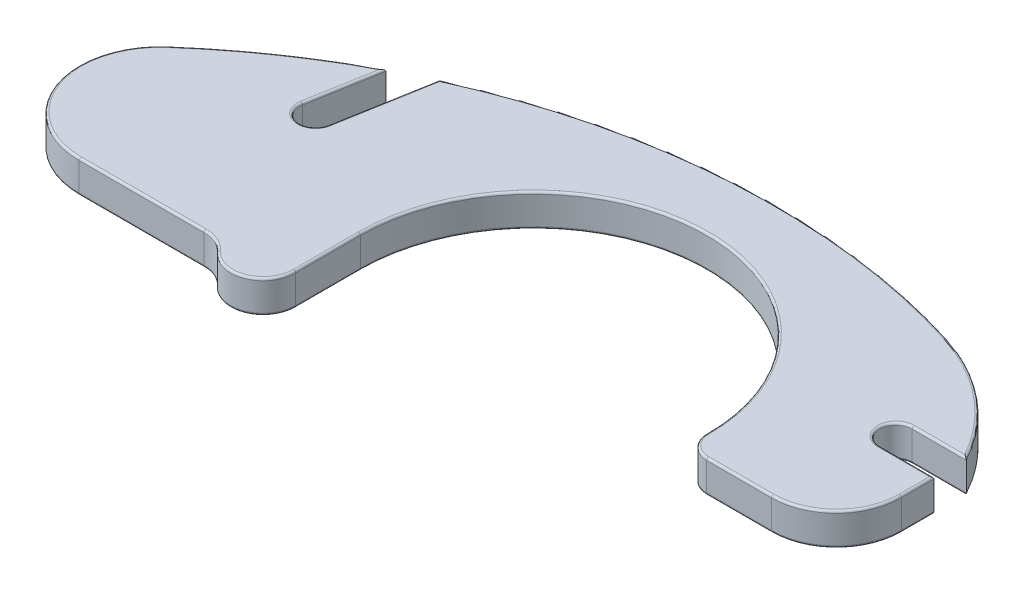
SolidWorks part; units mm, degrees
ref_plane "Front Plane" through (0, 0, 0) normal (0, 0, 1) x (1, 0, 0)
ref_plane "Top Plane" through (0, 0, 0) normal (0, 1, 0) x (1, 0, 0)
ref_plane "Right Plane" through (0, 0, 0) normal (1, 0, 0) x (0, 0, -1)
sketch "Sketch1" plane through (0, 0, 0) normal (0, 1, 0) x (1, 0, 0)
  line L1 (30, 5.5) -> (25, 5.5)
  line L2 (30, 8.5) -> (25, 8.5)
  line L4 (-24.6366, 14.4514) -> (-26.1728, 5.7395)
  line L5 (-27.9715, 12.8147) -> (-29.1272, 6.2605)
  line L8 (-35, -8.5) -> (-23.4721, -8.5)
  line L9 (24, -3.5) -> (18, -3.5)
  line L10 (30, 5.5) -> (30, 2.5)
  line L11 (-16, -1.5) -> (-16, -7.5)
  arc A0 (-23.4721, -8.5) -> (-21.2361, -9.5) centre (-23.4721, -11.5) cw
  arc A1 (-27.9715, 12.8147) -> (-39.9276, 4.5718) centre (1, -42) ccw
  arc A2 (25, 8.5) -> (25, 5.5) centre (25, 7) ccw
  arc A4 (-29.1272, 6.2605) -> (-26.1728, 5.7395) centre (-27.65, 6) ccw
  arc A5 (19.5159, 17.1706) -> (-24.6366, 14.4514) centre (1, -42) ccw
  arc A6 (16, -1.5) -> (-16, -1.5) centre (0, -1.5) ccw
  arc A7 (-21.2361, -9.5) -> (-16, -7.5) centre (-19, -7.5) ccw
  arc A8 (-39.9276, 4.5718) -> (-35, -8.5) centre (-35, -1.0353) ccw
  arc A9 (30, 8.5) -> (19.5159, 17.1706) centre (14.1428, 0) ccw
  arc A10 (30, 2.5) -> (24, -3.5) centre (24, 2.5) cw
  arc A12 (18, -3.5) -> (16, -1.5) centre (18, -1.5) cw
  dimension "D15" = 1.5
  dimension "D16" = 10
  dimension "D17" = 6
  dimension "D18" = 3
  dimension "D19" = 1
  dimension "D20" = 27.65
  dimension "D21" = 2
  dimension "D6" = 16
  dimension "D5" = 62
  dimension "D7" = 1
  dimension "D12" = 5.5
  dimension "D22" = 5
  dimension "D11" = 42
  dimension "D24" = 3
  dimension "D2" = 3
  dimension "D3" = 3
  dimension "D4" = 1.5
  dimension "D8" = 3.5
  dimension "D9" = 8.5
  dimension "D10" = 35
  dimension "D13" = 25
  dimension "D14" = 30
  dimension "D23" = 6
extrude "Boss-Extrude1" add sketch "Sketch1" along normal blind 3
fillet "Fillet2" radius 0.2 38 edges at (-27.9105, 0, -4.5228) (-28.5494, 0, -9.5376) (-25.4047, 0, -10.0955) (27.5, 0, -8.5) (27.5, 0, -5.5) (-29.2361, 0, 8.5) (-17.9295, 0, 10.3025) (-16, 0, 4.5) (16.5858, 0, 2.9142) (21, 0, 3.5) (28.2426, 0, 1.7426) (-2.8111, 0, -19.8828) (-28.5494, 3, -9.5376) (-27.9105, 3, -4.5228) (-25.4047, 3, -10.0955) (-2.8111, 3, -19.8828) (28.2426, 3, 1.7426) (21, 3, 3.5) (16.5858, 3, 2.9142) (-16, 3, 4.5) (-17.9295, 3, 10.3025) (-29.2361, 3, 8.5) (27.5, 3, -8.5) (27.5, 3, -5.5) (-34.1917, 0, -9.0445) (30, 0, -4) (23.5, 0, -7) (23.5, 3, -7) (30, 3, -4) (-34.1917, 3, -9.0445) (-41.9849, 0, 3.6684) (-41.9849, 3, 3.6684) (0, 0, -14.5) (0, 3, -14.5) (-22.2474, 0, 8.7614) (-22.2474, 3, 8.7614) (25.6091, 0, -13.8645) (25.6091, 3, -13.8645)
